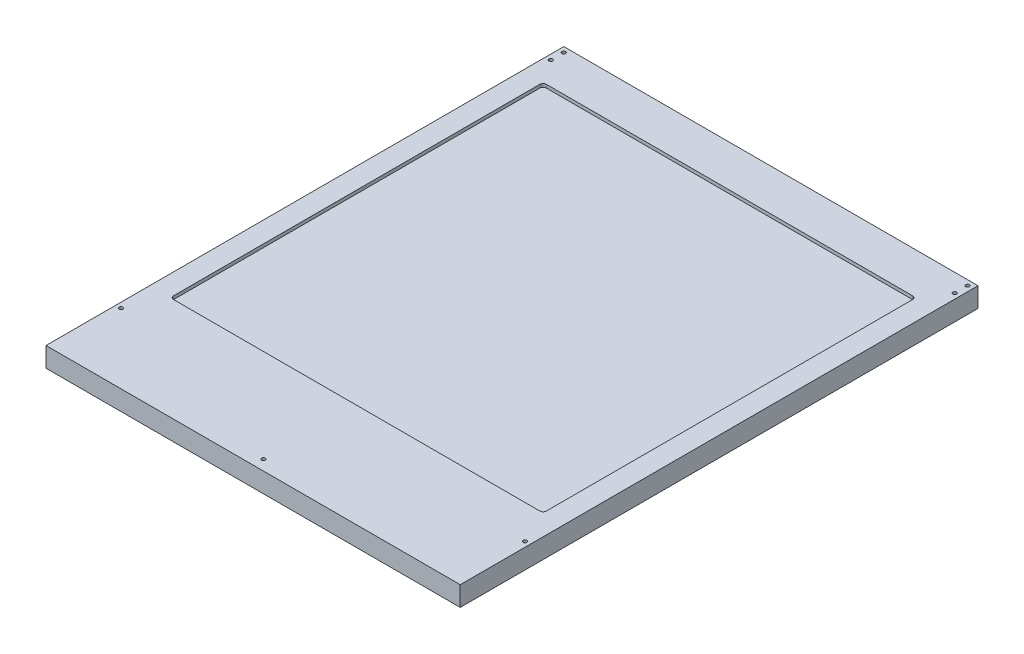
SolidWorks part; units mm, degrees
ref_plane "Front Plane" through (0, 0, 0) normal (0, 0, 1) x (1, 0, 0)
ref_plane "Top Plane" through (0, 0, 0) normal (0, 1, 0) x (1, 0, 0)
ref_plane "Right Plane" through (0, 0, 0) normal (1, 0, 0) x (0, 0, -1)
sketch "Sketch2" plane through (0, 0, 0) normal (0, 1, 0) x (1, 0, 0)
  line L1 (0, 0) -> (400, 0)
  line L2 (0, 0) -> (0, 500)
  line L3 (0, 500) -> (400, 500)
  line L4 (400, 0) -> (400, 500)
  dimension "D1" = 500
  dimension "D2" = 400
extrude "Boss-Extrude1" add sketch "Sketch2" along normal blind 19.05
sketch "Sketch3" plane through (0, 19.05, 0) normal (0, 1, 0) x (1, 0, 0)
  line L0 (200, 500) -> (200, 0) construction
  line L1 (400, 500) -> (0, 500) construction
  line L2 (0, 0) -> (400, 0) construction
  line L3 (0, 280) -> (400, 280) construction
  line L6 (20, 100) -> (20, 460)
  line L7 (20, 460) -> (380, 460)
  line L8 (380, 100) -> (380, 460)
  line L9 (20, 100) -> (380, 100)
  line L10 (400, 0) -> (400, 500) construction
  line L11 (0, 500) -> (0, 0) construction
  point P17 (200, 460)
  point P18 (380, 280)
  point P19 (20, 280)
  dimension "D1" = 360
  dimension "D2" = 360
  dimension "D3" = 40
extrude "Cut-Extrude1" cut sketch "Sketch3" against normal blind 3.175
fillet "Fillet1" radius 3.175 4 edges at (20, 17.4625, -100) (380, 17.4625, -100) (380, 17.4625, -460) (20, 17.4625, -460)
hole_wizard "M3 Clearance Hole1" positions "3DSketch1" profile "Sketch4" hole size "M3" standard "ANSI Metric" end condition through all
sketch3d "3DSketch1"
  line L0 (400, 19.05, -495) -> (395, 19.05, -495) construction
  line L1 (400, 19.05, 0) -> (400, 19.05, -500) construction
  line L2 (395, 19.05, -495) -> (395, 19.05, -500) construction
  line L3 (400, 19.05, -500) -> (0, 19.05, -500) construction
  line L5 (0, 19.05, -495) -> (5, 19.05, -495) construction
  line L6 (0, 19.05, -500) -> (0, 19.05, 0) construction
  line L7 (5, 19.05, -495) -> (5, 19.05, -500) construction
  line L9 (200, 19.05, 0) -> (200, 19.05, -500) construction
  line L10 (0, 19.05, 0) -> (400, 19.05, 0) construction
  point P0 (395, 19.05, -495)
  point P2 (5, 19.05, -495)
  point P4 (200, 19.05, -10)
  dimension "D1" = 5
  dimension "D2" = 5
  dimension "D3" = 450
sketch "Sketch4" plane through (395, 19.05, -495) normal (1, 0, 0) x (0, 0, 1)
  line L0 (0, 0) -> (0, 19.05)
  line L1 (0, 19.05) -> (1.8, 19.05)
  line L2 (1.8, 19.05) -> (1.8, 0)
  line L5 (1.8, 0) -> (0, 0)
  line L11 (0, -6.35) -> (0, 107.95) construction
  dimension "Thru Hole Dia." = 3.6
  dimension "Thru Hole Depth" = 19.05
hole_wizard "M3 Clearance Hole2" positions "3DSketch2" profile "Sketch5" hole size "M3" standard "ANSI Metric" end condition through all
sketch3d "3DSketch2"
  line L0 (395, 19.05, -482.5) -> (395, 19.05, -67.5) construction
  line L3 (5, 19.05, -482.5) -> (5, 19.05, -67.5) construction
  line L6 (400, 19.05, -500) -> (0, 19.05, -500) construction
  line L7 (400, 19.05, 0) -> (400, 19.05, -500) construction
  line L8 (0, 19.05, -500) -> (0, 19.05, 0) construction
  point P0 (395, 19.05, -482.5)
  point P2 (5, 19.05, -482.5)
  point P4 (5, 19.05, -67.5)
  point P6 (395, 19.05, -67.5)
  dimension "D1" = 17.5
  dimension "D2" = 5
  dimension "D3" = 5
  dimension "D4" = 415
sketch "Sketch5" plane through (395, 19.05, -482.5) normal (1, 0, 0) x (0, 0, 1)
  line L0 (0, 0) -> (0, 19.05)
  line L1 (0, 19.05) -> (1.8, 19.05)
  line L2 (1.8, 19.05) -> (1.8, 0)
  line L5 (1.8, 0) -> (0, 0)
  line L11 (0, -6.35) -> (0, 107.95) construction
  dimension "Thru Hole Dia." = 3.6
  dimension "Thru Hole Depth" = 19.05
